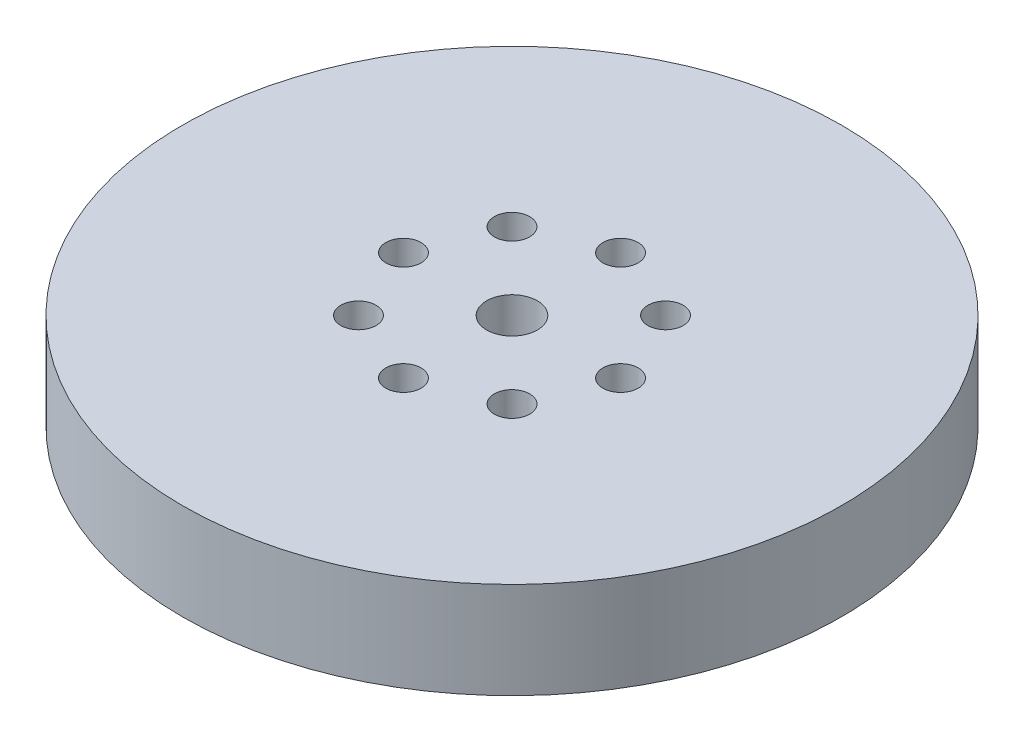
SolidWorks part; units mm, degrees
ref_plane "Front Plane" through (0, 0, 0) normal (0, 0, 1) x (1, 0, 0)
ref_plane "Top Plane" through (0, 0, 0) normal (0, 1, 0) x (1, 0, 0)
ref_plane "Right Plane" through (0, 0, 0) normal (1, 0, 0) x (0, 0, -1)
sketch "Sketch1" plane through (0, 0, 0) normal (0, 1, 0) x (1, 0, 0)
  circle A0 centre (0, 0) radius 65
  dimension "FLANGE_OD" = 130
extrude "Boss-Extrude1" add sketch "Sketch1" along normal blind 19
sketch "Sketch2" plane through (0, 0, 0) normal (0, 1, 0) x (1, 0, 0)
  circle A0 centre (0, 0) radius 5
  dimension "BORE_D" = 10
extrude "Cut-Extrude1" cut sketch "Sketch2" along normal through all
sketch "Sketch3" plane through (0, 19, 0) normal (0, 1, 0) x (1, 0, 0)
  circle A0 centre (0, 0) radius 21.4099 construction
  circle A1 centre (-21.4099, 0) radius 3.4796
  dimension "BOLT_D" = 6.9591
  dimension "BOLT_PCD" = 42.8199
extrude "Cut-Extrude2" cut sketch "Sketch3" against normal blind 11.751
pattern_circular "CirPattern1" count 8 over 360 about axis through (0, 0, 0) along (0, 1, 0) of "Cut-Extrude2"
